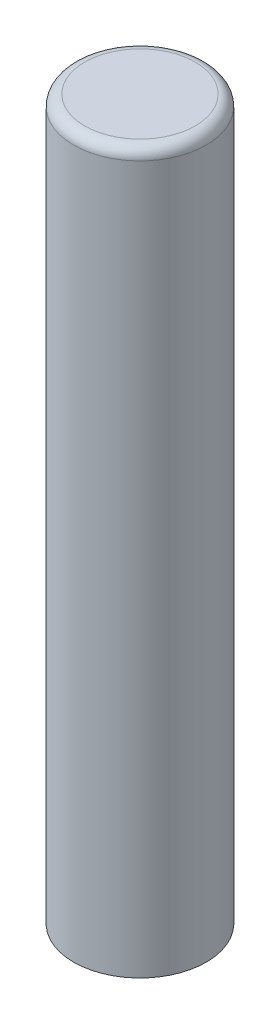
SolidWorks part; units mm, degrees
material "Mahogany"
ref_plane "Front Plane" through (0, 0, 0) normal (0, 0, 1) x (1, 0, 0)
ref_plane "Top Plane" through (0, 0, 0) normal (0, 1, 0) x (1, 0, 0)
ref_plane "Right Plane" through (0, 0, 0) normal (1, 0, 0) x (0, 0, -1)
sketch "Sketch2" plane through (0, 0, 0) normal (0, 1, 0) x (1, 0, 0)
  circle A0 centre (0, 0) radius 60
  dimension "D1" = 120
extrude "Boss-Extrude1" add sketch "Sketch2" along normal blind 650
fillet "Fillet1" radius 10 1 edges at (0, 650, 60)
ref_plane "Plane1" through (0, 0, 60) normal (0, 0, 1) x (1, 0, 0)
sketch "Sketch3" plane through (0, 0, 60) normal (0, 0, 1) x (1, 0, 0)
  line L0 (0, 505.4068) -> (0, 362.6266) construction
  line L1 (-71.4387, 550) -> (74.0611, 550) construction
  line L2 (50, 650) -> (-50, 650) construction
  point P5 (0, 550)
  point P8 (0, 362.6266)
  point P9 (0, 0)
  point P10 (0, 0)
  dimension "D1" = 100
ref_axis "Body-Axis" through (0, 640, 0) along (0, -1, 0)
ref_axis "Shoulder-axis" through (0, 550, 60) along (0, 0, 1)
